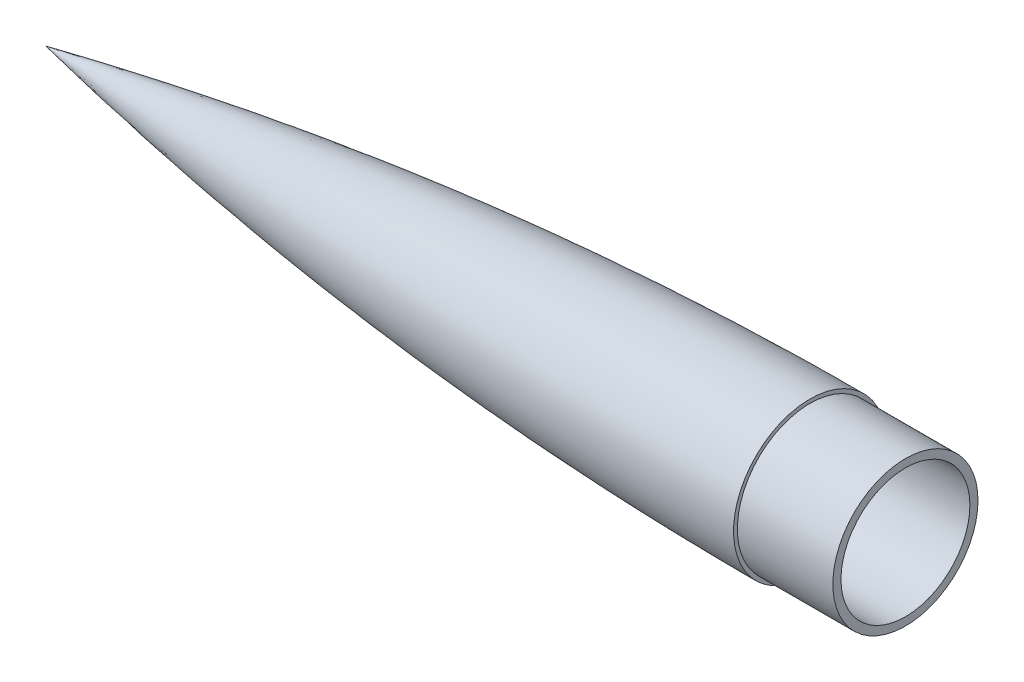
SolidWorks part; units mm, degrees
ref_plane "Front Plane" through (0, 0, 0) normal (0, 0, 1) x (1, 0, 0)
ref_plane "Top Plane" through (0, 0, 0) normal (0, 1, 0) x (1, 0, 0)
ref_plane "Right Plane" through (0, 0, 0) normal (1, 0, 0) x (0, 0, -1)
sketch "Sketch1" plane through (0, 0, 0) normal (0, 0, 1) x (1, 0, 0)
  line L0 (0, 1026.16) -> (0, 1005.84)
  line L1 (0, 1005.84) -> (-203.2, 1005.84)
  arc A0 (0, 1026.16) -> (-203.2, 1005.84) centre (0, 0) ccw
  arc A1 (-203.2, 1005.84) -> (0, 1026.16) centre (0, 0) ccw construction
  dimension "D1" = 20.32
  dimension "D2" = 203.2
revolve "Revolve1" add sketch "Sketch1" angle 360 about L1
shell "Shell1" thickness 3.175 removed face at (0, 1005.84, -20.32)
sketch "Sketch2" plane through (0, 0, 0) normal (1, 0, 0) x (0, 0, -1)
  circle A0 centre (0, 1005.84) radius 17.145 construction
  circle A1 centre (0, 1005.84) radius 17.145
  circle A2 centre (0, 1005.84) radius 19.304
  dimension "D1" = 38.608
extrude "Boss-Extrude1" add sketch "Sketch2" along normal mid plane 50.8
